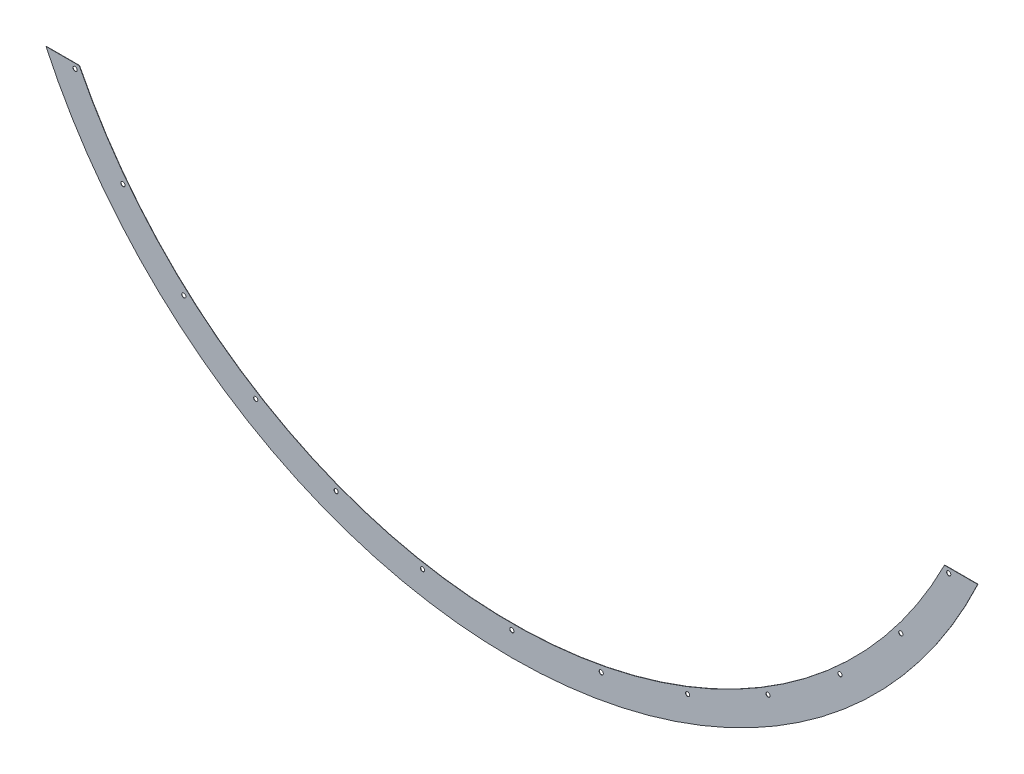
SolidWorks part; units mm, degrees
note: The reader was unsure of these and kept them because the rebuilt part matched: thickness of "Base-Flange1", "Sheet-Metal3", "Sheet-Metal4", "Sheet-Metal8", "Sheet-Metal9", "Sheet-Metal10".
material "AISI 304"
ref_plane "Front Plane" through (0, 0, 0) normal (0, 0, 1) x (1, 0, 0)
ref_plane "Top Plane" through (0, 0, 0) normal (0, 1, 0) x (1, 0, 0)
ref_plane "Right Plane" through (0, 0, 0) normal (1, 0, 0) x (0, 0, -1)
sketch "Sketch1" plane through (0, 0, 0) normal (0, 0, 1) x (1, 0, 0)
  line L0 (859.9855, -5) -> (-859.9855, -5)
  arc A0 (-859.9855, -5) -> (859.9855, -5) centre (0, 0) ccw
  dimension "D1" = 1720
  dimension "D2" = 5
base flange "Base-Flange1" sketch "Sketch1" thickness 0.5 reverse thickness direction no parameters "D1"=0
sketch "Sketch2" plane through (0, 0, 0) normal (0, 0, 1) x (1, 0, 0)
  line L1 (-973.8714, 418.1233) -> (994.6473, 418.1233)
  line L2 (-973.8714, 418.1233) -> (-973.8714, -364)
  line L3 (-973.8714, -364) -> (994.6473, -364)
  line L4 (994.6473, 418.1233) -> (994.6473, -364)
  dimension "D1" = 364
extrude "Cut-Extrude1" cut sketch "Sketch2" against normal blind 10 normal cut yes
sketch "Sketch9" plane through (0, 0, 0) normal (0, 0, 1) x (1, 0, 0)
  line L0 (-723.6049, -364) -> (723.6049, -364)
  line L1 (-779.1688, -364) -> (779.1688, -364) construction
  arc A0 (-723.6049, -364) -> (723.6049, -364) centre (0, 0) ccw
  dimension "D1" = 1620
extrude "Cut-Extrude3" cut sketch "Sketch9" against normal blind 10 normal cut yes
sketch "Sketch10" plane through (0, 0, -0.5) normal (0, 0, -1) x (-1, 0, 0)
  circle A0 centre (0, -820) radius 3.5
  dimension "D1" = 7
  dimension "D2" = 820
extrude "Cut-Extrude4" cut sketch "Sketch10" against normal blind 10 normal cut yes
pattern_circular "CirPattern1" count 10 every 10.5 about axis through (0, 0, 0) along (0, 0, 1) of "Cut-Extrude4"
sketch "Bend-Lines1" [suppressed] plane through (0, 0, 0) normal (0, 1, 0) x (1, 0, 0)
sketch "Bounding-Box1" [suppressed] plane through (0, 0, 0) normal (0, 1, 0) x (1, 0, 0)
sheet metal parameters "Sheet-Metal3" thickness 0.5 parameters "D1"=0
flat pattern "Flat-Pattern3" [suppressed]
sketch "Bend-Lines2" plane through (0, 0, 0) normal (0, 1, 0) x (1, 0, 0)
sketch3d "Bounding-Box2" [suppressed]
  line L0 (789.9842, -5, 0) -> (-789.9842, -5, 0) construction
  line L1 (789.9842, -789.9999, 0) -> (-789.9842, -789.9999, 0) construction
  line L2 (789.9842, -5, 0) -> (789.9842, -789.9999, 0) construction
  line L3 (-789.9842, -5, 0) -> (-789.9842, -789.9999, 0) construction
sheet metal parameters "Sheet-Metal4" thickness 0.5 parameters "D1"=0, "D7"=6
flat pattern "Flat-Pattern3" [suppressed]
sketch "Bend-Lines2" plane through (0, 0, 0) normal (0, 1, 0) x (1, 0, 0)
sketch3d "Bounding-Box2" [suppressed]
  line L0 (-757.0363, -840, 0) -> (757.0363, -840, 0) construction
  line L1 (-757.0363, -364, 0) -> (757.0363, -364, 0) construction
  line L2 (-757.0363, -840, 0) -> (-757.0363, -364, 0) construction
  line L3 (757.0363, -840, 0) -> (757.0363, -364, 0) construction
sketch "Sketch3-1" [suppressed] plane through (0, 0, -2) normal (0, 0, -1) x (-1, 0, 0)
  line L0 (-742.0363, -364) -> (742.0363, -364)
  arc A0 (-742.0363, -364) -> (742.0363, -364) centre (0, 7.863) ccw
  dimension "D3" = 830
  dimension "D1" = 15
  dimension "D2" = 15
sheet metal parameters "Sheet-Metal8" thickness 0.5 parameters "D1"=0, "D7"=6
flat pattern "Flat-Pattern3"
sketch "Bend-Lines2" plane through (0, 0, 0) normal (0, 1, 0) x (1, 0, 0)
sketch3d "Bounding-Box2" [suppressed]
  line L0 (-784.684, -865, 0) -> (784.684, -865, 0) construction
  line L1 (-784.684, -364, 0) -> (784.684, -364, 0) construction
  line L2 (-784.684, -865, 0) -> (-784.684, -364, 0) construction
  line L3 (784.684, -865, 0) -> (784.684, -364, 0) construction
sheet metal parameters "Sheet-Metal9" thickness 0.5 parameters "D1"=0, "D7"=6
flat pattern "Flat-Pattern3"
sketch "Bend-Lines2" plane through (0, 0, 0) normal (0, 1, 0) x (1, 0, 0)
sketch3d "Bounding-Box2" [suppressed]
  line L0 (-784.684, -865, 0) -> (784.684, -865, 0) construction
  line L1 (-784.684, -364, 0) -> (784.684, -364, 0) construction
  line L2 (-784.684, -865, 0) -> (-784.684, -364, 0) construction
  line L3 (784.684, -865, 0) -> (784.684, -364, 0) construction
sheet metal parameters "Sheet-Metal10" thickness 0.5 parameters "D1"=0, "D7"=6
flat pattern "Flat-Pattern3"
sketch "Bend-Lines2" plane through (0, 0, 0) normal (0, 1, 0) x (1, 0, 0)
sketch3d "Bounding-Box2" [suppressed]
  line L0 (-779.1688, -860, 0) -> (779.1688, -860, 0) construction
  line L1 (-779.1688, -364, 0) -> (779.1688, -364, 0) construction
  line L2 (-779.1688, -860, 0) -> (-779.1688, -364, 0) construction
  line L3 (779.1688, -860, 0) -> (779.1688, -364, 0) construction
